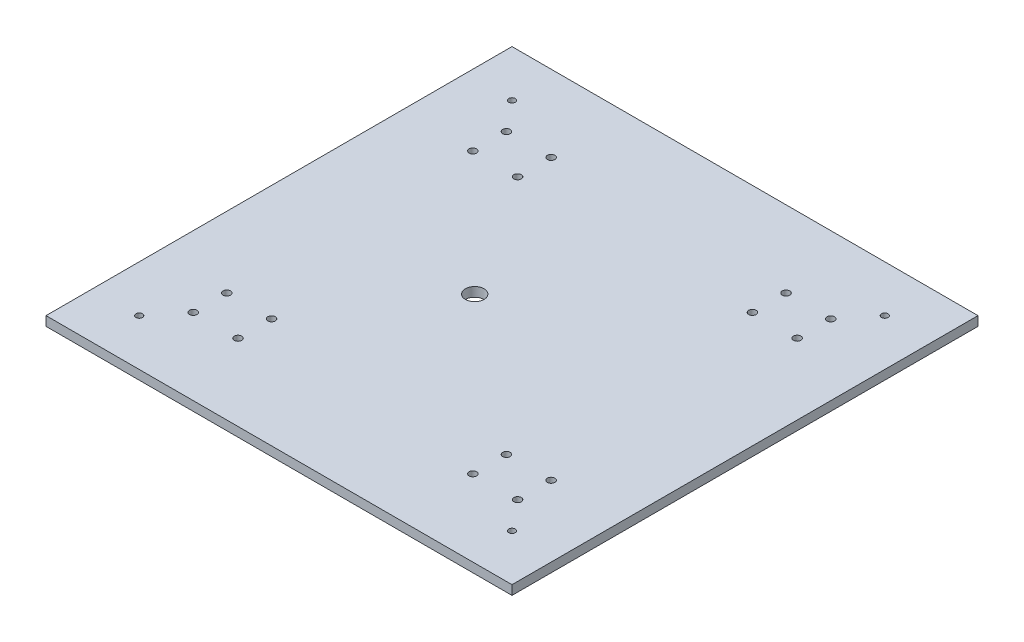
SolidWorks part; units mm, degrees
ref_plane "Front Plane" through (0, 0, 0) normal (0, 0, 1) x (1, 0, 0)
ref_plane "Top Plane" through (0, 0, 0) normal (0, 1, 0) x (1, 0, 0)
ref_plane "Right Plane" through (0, 0, 0) normal (1, 0, 0) x (0, 0, -1)
sketch "Sketch1" plane through (0, 0, 0) normal (0, 1, 0) x (1, 0, 0)
  line L0 (-87, 84) -> (-63, 66) construction
  line L1 (-125, -125) -> (125, -125)
  line L2 (-125, -125) -> (-125, 125)
  line L3 (-125, 125) -> (125, 125)
  line L4 (125, -125) -> (125, 125)
  line L5 (-125, -125) -> (125, 125) construction
  line L6 (-125, 125) -> (125, -125) construction
  line L7 (-63, 66) -> (-87, 66) construction
  line L8 (-87, 66) -> (-63, 84) construction
  line L9 (-63, 84) -> (-87, 84) construction
  line L10 (-87, 84) -> (-87, 66) construction
  line L11 (-63, 84) -> (-63, 66) construction
  line L12 (63, 84) -> (87, 66) construction
  line L13 (87, 66) -> (63, 66) construction
  line L14 (63, 66) -> (87, 84) construction
  line L15 (87, 84) -> (63, 84) construction
  line L16 (63, 84) -> (63, 66) construction
  line L17 (87, 84) -> (87, 66) construction
  line L18 (-87, -66) -> (-63, -84) construction
  line L19 (-63, -84) -> (-87, -84) construction
  line L20 (-87, -84) -> (-63, -66) construction
  line L21 (-63, -66) -> (-87, -66) construction
  line L22 (-87, -66) -> (-87, -84) construction
  line L23 (-63, -66) -> (-63, -84) construction
  line L24 (63, -66) -> (87, -84) construction
  line L25 (87, -84) -> (63, -84) construction
  line L26 (63, -84) -> (87, -66) construction
  line L27 (87, -66) -> (63, -66) construction
  line L28 (63, -66) -> (63, -84) construction
  line L29 (87, -66) -> (87, -84) construction
  line L30 (75, 75) -> (-75, 75) construction
  line L31 (-75, 75) -> (-75, -75) construction
  line L32 (-75, -75) -> (75, -75) construction
  line L33 (75, -75) -> (75, 75) construction
  line L34 (-100, 100) -> (100, 100) construction
  line L35 (100, 100) -> (100, -100) construction
  line L36 (100, -100) -> (-100, -100) construction
  line L37 (-100, -100) -> (-100, 100) construction
  line L38 (0, 0) -> (-20, 0) construction
  circle A0 centre (-100, 100) radius 1.75
  circle A1 centre (100, 100) radius 1.75
  circle A2 centre (100, -100) radius 1.75
  circle A3 centre (-100, -100) radius 1.75
  circle A4 centre (-87, 84) radius 2
  circle A5 centre (-87, 66) radius 2
  circle A6 centre (-63, 84) radius 2
  circle A7 centre (-63, 66) radius 2
  circle A8 centre (63, 84) radius 2
  circle A9 centre (63, 66) radius 2
  circle A10 centre (87, 84) radius 2
  circle A11 centre (87, 66) radius 2
  circle A12 centre (-87, -66) radius 2
  circle A13 centre (-87, -84) radius 2
  circle A14 centre (-63, -66) radius 2
  circle A15 centre (-63, -84) radius 2
  circle A16 centre (63, -66) radius 2
  circle A17 centre (63, -84) radius 2
  circle A18 centre (87, -66) radius 2
  circle A19 centre (87, -84) radius 2
  circle A20 centre (-20, 0) radius 5
  point P0 (0, 0)
  point P23 (-75, 75)
  point P32 (75, 75)
  point P41 (-75, -75)
  point P50 (75, -75)
  dimension "D3" = 3.5
  dimension "D4" = 200
  dimension "D6" = 4
  dimension "D7" = 24
  dimension "D9" = 4
  dimension "D12" = 4
  dimension "D15" = 4
  dimension "D20" = 10
  dimension "D1" = 250
  dimension "D2" = 250
  dimension "D5" = 200
  dimension "D8" = 18
  dimension "D10" = 24
  dimension "D11" = 18
  dimension "D13" = 24
  dimension "D14" = 18
  dimension "D16" = 24
  dimension "D17" = 18
  dimension "D18" = 150
  dimension "D19" = 20
extrude "Boss-Extrude1" add sketch "Sketch1" along normal blind 5
sketch3d "3DSketch1"
  point P0 (-82.7094, 0, 5.8034)
sketch3d "3DSketch2"
  point P0 (84.72, 0, 15.1659)
ref_plane "buttom" through (0, 0, 0) normal (0, -1, 0) x (1, 0, 0)
sketch "Sketch2" plane through (0, 0, 0) normal (0, -1, 0) x (1, 0, 0)
  line L0 (125, 125) -> (-125, -125) construction
  line L1 (-125, 125) -> (125, -125) construction
  line L2 (0, 125) -> (0, -125) construction
  line L3 (-125, 125) -> (125, 125) construction
  line L4 (125, -125) -> (-125, -125) construction
  line L5 (-20, 0) -> (0, 0) construction
  line L10 (10, 112.5) -> (-10, 112.5)
  line L11 (10, 112.5) -> (10, 107.5)
  line L16 (10, 107.5) -> (-10, 107.5)
  line L17 (-10, 112.5) -> (-10, 107.5)
  line L18 (10, 112.5) -> (-10, 107.5) construction
  line L19 (10, 107.5) -> (-10, 112.5) construction
  line L20 (10, -107.5) -> (-10, -112.5) construction
  line L21 (10, -112.5) -> (-10, -107.5) construction
  line L22 (-10, -112.5) -> (-10, -107.5)
  line L23 (10, -107.5) -> (-10, -107.5)
  line L24 (10, -112.5) -> (10, -107.5)
  line L25 (10, -112.5) -> (-10, -112.5)
  point P14 (0, 110)
  point P27 (0, -110)
  dimension "D1" = 5
  dimension "D2" = 20
  dimension "D3" = 15
extrude "Boss-Extrude2" add sketch "Sketch2" along normal blind 10
sketch3d "3DSketch3"
  point P0 (-10, -5.5879, 110.015)
ref_plane "Plane4" through (-10, 0, 0) normal (-1, 0, 0) x (0, 0, 1)
sketch "Sketch4" plane through (-10, 0, 0) normal (-1, 0, 0) x (0, 0, 1)
  line L0 (112.5, -10) -> (118.2735, 0)
  line L1 (-125, 0) -> (125, 0) construction
  line L3 (112.5, 0) -> (118.2735, 0)
  line L8 (112.5, 0) -> (107.5, 0)
  line L9 (107.5, 0) -> (107.5, -10)
  line L10 (107.5, -10) -> (112.5, -10)
  line L11 (112.5, -10) -> (112.5, 0)
  line L15 (112.5, -10) -> (112.5, 0)
  dimension "D1" = 60
  dimension "D2" = 0
extrude "Boss-Extrude7" add sketch "Sketch4" against normal blind 20
sketch "Sketch5" plane through (0, 0, -112.5) normal (0, 0, -1) x (-1, 0, 0)
  line L0 (-10, 0) -> (10, -10) construction
  line L1 (10, -10) -> (10, 0) construction
  line L2 (10, -2.75) -> (10, 2.75) construction
  line L3 (-10, -10) -> (10, 0) construction
  line L4 (10, -10) -> (-10, -10) construction
  line L5 (-4, -5) -> (4, -5) construction
  line L6 (-4, -3.3) -> (4, -3.3)
  line L7 (-4, -6.7) -> (4, -6.7)
  arc A0 (-4, -3.3) -> (-4, -6.7) centre (-4, -5) ccw
  arc A1 (4, -6.7) -> (4, -3.3) centre (4, -5) ccw
  point P14 (0, -5)
  point P19 (0, -5.0385)
  point P20 (0, 0)
  point P21 (0, 0)
  point P22 (-10, -10)
  dimension "D1" = 8
  dimension "D2" = 3.4
